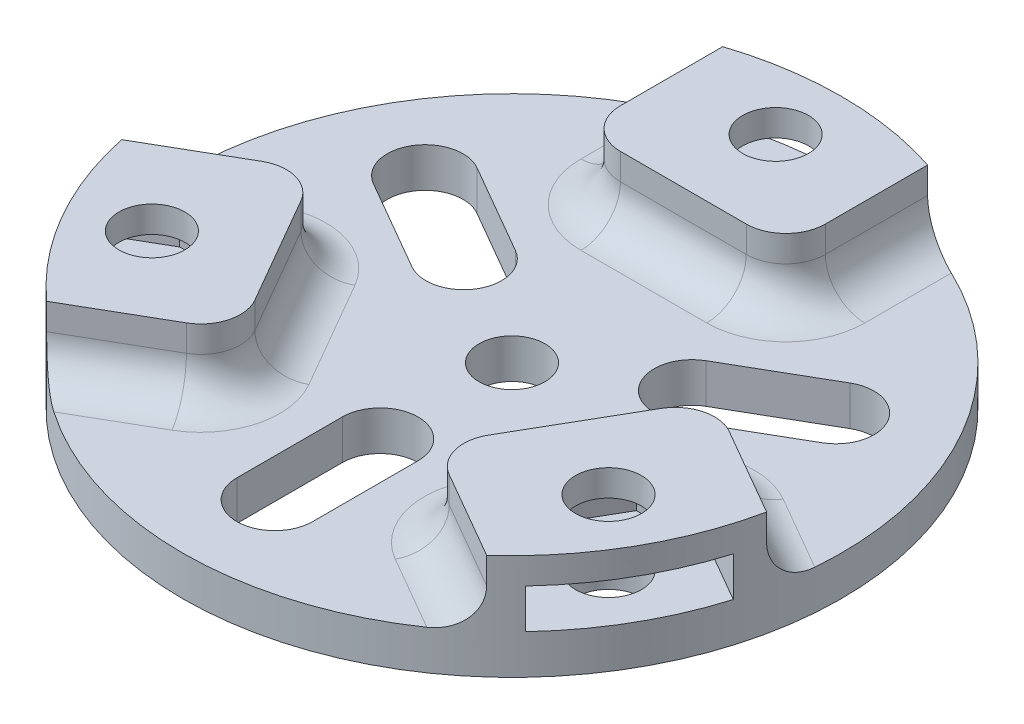
SolidWorks part; units mm, degrees
ref_plane "Front Plane" through (0, 0, 0) normal (0, 0, 1) x (1, 0, 0)
ref_plane "Top Plane" through (0, 0, 0) normal (0, 1, 0) x (1, 0, 0)
ref_plane "Right Plane" through (0, 0, 0) normal (1, 0, 0) x (0, 0, -1)
sketch "Sketch1" plane through (0, 0, 0) normal (0, 1, 0) x (1, 0, 0)
  line L0 (0, 0) -> (0, 20) construction
  circle A0 centre (0, 0) radius 25
  circle A1 centre (0, 20) radius 2.5
  circle A2 centre (17.3205, -10) radius 2.5
  circle A3 centre (-17.3205, -10) radius 2.5
  circle A4 centre (0, 0) radius 2.5
  point P12 (0, 0)
  dimension "D1" = 50
  dimension "D2" = 5
  dimension "D5" = 5
  dimension "D3" = 20
  dimension "D4" = 3
extrude "Boss-Extrude1" add sketch "Sketch1" along normal blind 3
sketch "Sketch2" plane through (0, 3, 0) normal (0, 1, 0) x (1, 0, 0)
  line L0 (-5.7735, 20) -> (-5.7735, 24.3242)
  line L1 (5.7735, 20) -> (2.8868, 25)
  line L2 (2.8868, 25) -> (-2.8868, 25)
  line L3 (-2.8868, 25) -> (-5.7735, 20)
  line L4 (-5.7735, 20) -> (-2.8868, 15)
  line L5 (-2.8868, 15) -> (2.8868, 15)
  line L6 (2.8868, 15) -> (5.7735, 20)
  line L7 (7.7735, 27) -> (-7.7735, 27)
  line L8 (7.7735, 27) -> (7.7735, 13)
  line L9 (7.7735, 13) -> (-7.7735, 13)
  line L10 (-7.7735, 27) -> (-7.7735, 13)
  line L11 (7.7735, 27) -> (-7.7735, 13) construction
  line L12 (7.7735, 13) -> (-7.7735, 27) construction
  line L13 (5.7735, 20) -> (5.7735, 24.3242)
  line L14 (20.2073, -5) -> (23.9521, -7.1621)
  line L15 (14.4338, -15) -> (20.2073, -15)
  line L16 (20.2073, -15) -> (23.094, -10)
  line L17 (23.094, -10) -> (20.2073, -5)
  line L18 (20.2073, -5) -> (14.4338, -5)
  line L19 (14.4338, -5) -> (11.547, -10)
  line L20 (11.547, -10) -> (14.4338, -15)
  line L21 (19.4959, -20.2321) -> (27.2694, -6.7679)
  line L22 (19.4959, -20.2321) -> (7.3716, -13.2321)
  line L23 (7.3716, -13.2321) -> (15.1451, 0.2321)
  line L24 (27.2694, -6.7679) -> (15.1451, 0.2321)
  line L25 (14.4338, -15) -> (18.1786, -17.1621)
  line L26 (19.4959, -20.2321) -> (15.1451, 0.2321) construction
  line L27 (7.3716, -13.2321) -> (27.2694, -6.7679) construction
  line L28 (-14.4338, -15) -> (-18.1786, -17.1621)
  line L29 (-20.2073, -5) -> (-23.094, -10)
  line L30 (-23.094, -10) -> (-20.2073, -15)
  line L31 (-20.2073, -15) -> (-14.4338, -15)
  line L32 (-14.4338, -15) -> (-11.547, -10)
  line L33 (-11.547, -10) -> (-14.4338, -5)
  line L34 (-14.4338, -5) -> (-20.2073, -5)
  line L35 (-27.2694, -6.7679) -> (-19.4959, -20.2321)
  line L36 (-27.2694, -6.7679) -> (-15.1451, 0.2321)
  line L37 (-15.1451, 0.2321) -> (-7.3716, -13.2321)
  line L38 (-19.4959, -20.2321) -> (-7.3716, -13.2321)
  line L39 (-20.2073, -5) -> (-23.9521, -7.1621)
  line L40 (-27.2694, -6.7679) -> (-7.3716, -13.2321) construction
  line L41 (-15.1451, 0.2321) -> (-19.4959, -20.2321) construction
  circle A0 centre (0, 20) radius 5 construction
  circle A1 centre (0, 0) radius 25 construction
  arc A2 (-7.7735, 23.7607) -> (7.7735, 23.7607) centre (0, 0) cw
  arc A3 (24.4642, -5.1483) -> (16.6907, -18.6124) centre (0, 0) cw
  circle A4 centre (17.3205, -10) radius 5 construction
  arc A5 (-16.6907, -18.6124) -> (-24.4642, -5.1483) centre (0, 0) cw
  circle A6 centre (-17.3205, -10) radius 5 construction
  point P55 (0, 0)
  dimension "D1" = 2
  dimension "D2" = 2
  dimension "D3" = 3
extrude "Boss-Extrude2" add sketch "Sketch2" along normal blind 3 contours L13 L6 L5 L4 L0 L41 L10 L9 L8 | L39 L34 L33 L32 L28 L41 L38 L37 L36 | L25 L20 L19 L18 L14 L41 L24 L23 L22
sketch "Sketch3" plane through (0, 6, 0) normal (0, 1, 0) x (1, 0, 0)
  line L0 (15.1451, 0.2321) -> (7.3716, -13.2321)
  line L1 (-7.7735, 13) -> (7.7735, 13)
  line L2 (-7.7735, 13) -> (-7.7735, 25)
  line L3 (-7.7735, 25) -> (7.7735, 25)
  line L4 (7.7735, 13) -> (7.7735, 25)
  line L5 (15.1451, 0.2321) -> (25.5374, -5.7679)
  line L6 (25.5374, -5.7679) -> (17.7639, -19.2321)
  line L7 (7.3716, -13.2321) -> (17.7639, -19.2321)
  line L8 (-7.3716, -13.2321) -> (-15.1451, 0.2321)
  line L9 (-7.3716, -13.2321) -> (-17.7639, -19.2321)
  line L10 (-17.7639, -19.2321) -> (-25.5374, -5.7679)
  line L11 (-15.1451, 0.2321) -> (-25.5374, -5.7679)
  arc A0 (5.7735, 24.3242) -> (-5.7735, 24.3242) centre (0, 0) ccw construction
  arc A1 (-7.7735, 23.7607) -> (7.7735, 23.7607) centre (0, 0) cw
  circle A2 centre (0, 20) radius 2.5
  arc A3 (24.4642, -5.1483) -> (16.6907, -18.6124) centre (0, 0) cw
  circle A4 centre (17.3205, -10) radius 2.5
  arc A5 (-16.6907, -18.6124) -> (-24.4642, -5.1483) centre (0, 0) cw
  circle A6 centre (-17.3205, -10) radius 2.5
  point P35 (0, 0)
  dimension "D1" = 3
extrude "Boss-Extrude3" add sketch "Sketch3" along normal blind 2 contours A0 A2 L0 L5 L6 L7 L8 L9 L10 L11 | A1 L7 L6 L5 L0 A2 | A5 L9 L8 L11 A6 | A3 L5 L0 L7 A4
sketch "Sketch4" plane through (0, 3, 0) normal (0, 1, 0) x (1, 0, 0)
  line L0 (0, -10) -> (0, -18) construction
  line L1 (2.8765, -10) -> (2.8765, -18)
  line L2 (-2.8765, -10) -> (-2.8765, -18)
  line L3 (-8.6603, 5) -> (-15.5885, 9) construction
  line L4 (-10.0985, 2.5089) -> (-17.0267, 6.5089)
  line L5 (-7.222, 7.4911) -> (-14.1502, 11.4911)
  line L6 (8.6603, 5) -> (15.5885, 9) construction
  line L7 (7.222, 7.4911) -> (14.1502, 11.4911)
  line L8 (10.0985, 2.5089) -> (17.0267, 6.5089)
  arc A3 (2.8765, -10) -> (-2.8765, -10) centre (0, -10) ccw
  arc A4 (-2.8765, -18) -> (2.8765, -18) centre (0, -18) ccw
  arc A5 (-10.0985, 2.5089) -> (-7.222, 7.4911) centre (-8.6603, 5) ccw
  arc A6 (-14.1502, 11.4911) -> (-17.0267, 6.5089) centre (-15.5885, 9) ccw
  arc A7 (7.222, 7.4911) -> (10.0985, 2.5089) centre (8.6603, 5) ccw
  arc A8 (17.0267, 6.5089) -> (14.1502, 11.4911) centre (15.5885, 9) ccw
  point P3 (0, -14)
  point P14 (-12.1244, 7)
  point P21 (12.1244, 7)
  point P26 (0, 0)
  dimension "D1" = 10
  dimension "D2" = 8
  dimension "D3" = 3
extrude "Cut-Extrude1" cut sketch "Sketch4" against normal up to next
fillet "Fillet1" radius 3 15 edges at (7.7735, 3, -18.3804) (-7.7735, 3, -18.3804) (-19.8046, 3, 2.4581) (-12.0311, 3, 15.9222) (12.0311, 3, 15.9222) (19.8046, 3, 2.4581) (0, 3, -13) (-11.2583, 3, 6.5) (11.2583, 3, 6.5) (15.1451, 5.5, -0.2321) (-15.1451, 5.5, -0.2321) (-7.3716, 5.5, 13.2321) (7.3716, 5.5, 13.2321) (7.7735, 5.5, -13) (-7.7735, 5.5, -13)
